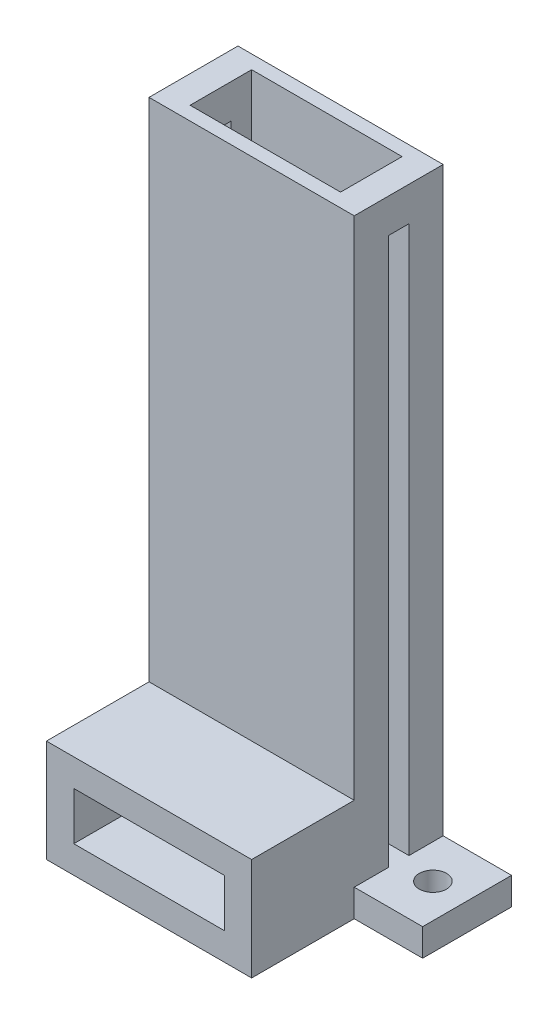
SolidWorks part; units mm, degrees
ref_plane "Front Plane" through (0, 0, 0) normal (0, 0, 1) x (1, 0, 0)
ref_plane "Top Plane" through (0, 0, 0) normal (0, 1, 0) x (1, 0, 0)
ref_plane "Right Plane" through (0, 0, 0) normal (1, 0, 0) x (0, 0, -1)
sketch "Sketch1" plane through (0, 0, 0) normal (0, 1, 0) x (1, 0, 0)
  line L1 (0, 0) -> (30, 0)
  line L2 (0, 0) -> (0, -13)
  line L3 (0, -13) -> (30, -13)
  line L4 (30, 0) -> (30, -13)
  dimension "D1" = 30
  dimension "D2" = 13
extrude "Boss-Extrude1" add sketch "Sketch1" along normal blind 85
sketch "Sketch2" plane through (0, 85, 0) normal (0, 1, 0) x (1, 0, 0)
  line L0 (0, -6.5) -> (30, -6.5) construction
  line L1 (0, 0) -> (0, -13) construction
  line L2 (30, -13) -> (30, 0) construction
  line L4 (4, -11) -> (26, -11)
  line L5 (4, -11) -> (4, -2)
  line L6 (4, -2) -> (26, -2)
  line L7 (26, -11) -> (26, -2)
  line L8 (4, -11) -> (26, -2) construction
  line L9 (4, -2) -> (26, -11) construction
  point P6 (15, -6.5)
  dimension "D1" = 22
  dimension "D2" = 9
extrude "Cut-Extrude2" cut sketch "Sketch2" against normal blind 85
sketch "Sketch5" plane through (0, 0, 0) normal (0, 1, 0) x (1, 0, 0)
  line L1 (0, 0) -> (30, 0)
  line L2 (0, 0) -> (0, -13)
  line L3 (0, -13) -> (30, -13)
  line L4 (30, 0) -> (30, -13)
extrude "Boss-Extrude3" add sketch "Sketch5" against normal blind 4
sketch "Sketch7" plane through (0, 85, 0) normal (0, 1, 0) x (1, 0, 0)
  line L0 (4, -13) -> (4, 0) construction
  line L1 (0, -13) -> (30, -13) construction
  line L2 (30, 0) -> (0, 0) construction
  line L3 (26, -13) -> (26, 0) construction
sketch "Sketch10" plane through (0, 85, 0) normal (0, 1, 0) x (1, 0, 0)
  line L0 (4, -13) -> (0, -13) construction
sketch "Sketch12" plane through (0, 0, 13) normal (0, 0, 1) x (1, 0, 0)
  line L0 (0, -4) -> (0, 0) construction
  line L1 (0, 85) -> (0, -4) construction
  line L2 (0, -4) -> (4, -4) construction
  line L3 (0, -4) -> (30, -4) construction
  line L4 (4, -4) -> (4, 0) construction
  line L5 (4, 0) -> (4, 7) construction
  line L7 (4, 0) -> (26, 0)
  line L8 (4, 0) -> (4, 7)
  line L9 (4, 7) -> (26, 7)
  line L10 (26, 0) -> (26, 7)
  dimension "D1" = 22
extrude "Cut-Extrude4" cut sketch "Sketch12" against normal blind 13 contours L9 L10 L7 L8
sketch "Sketch13" plane through (0, 0, 0) normal (-1, 0, 0) x (0, 0, 1)
  line L0 (0, -4) -> (13, -4) construction
  line L1 (5, -4) -> (8, -4) construction
  line L2 (6.5, -4) -> (6.5, 0) construction
  line L3 (6.5, 0) -> (5, 0) construction
  line L5 (5, 0) -> (8, 0)
  line L6 (5, 0) -> (5, 80)
  line L7 (5, 80) -> (8, 80)
  line L8 (8, 0) -> (8, 80)
  point P7 (6.5, -4)
  dimension "D1" = 3
  dimension "D2" = 80
extrude "Cut-Extrude5" cut sketch "Sketch13" against normal through all
sketch "Sketch14" plane through (0, 0, 13) normal (0, 0, 1) x (1, 0, 0)
  line L0 (30, 85) -> (30, -4) construction
  line L1 (4, 7) -> (26, 7) construction
  line L2 (4, 7) -> (4, 0) construction
  line L3 (4, 0) -> (26, 0) construction
  line L4 (26, 7) -> (26, 0) construction
  line L5 (0, -4) -> (30, -4)
  line L6 (0, -4) -> (0, 11)
  line L7 (0, 11) -> (30, 11)
  line L8 (30, -4) -> (30, 11)
  line L9 (26, 3.5) -> (30, 3.5) construction
  line L10 (15, 7) -> (15, 11) construction
extrude "Boss-Extrude4" add sketch "Sketch14" along normal blind 15
sketch "Sketch15" plane through (0, 0, 28) normal (0, 0, 1) x (1, 0, 0)
  line L0 (0, 3.5) -> (4, 3.5) construction
  line L1 (0, 11) -> (0, -4) construction
  line L2 (15, -4) -> (15, 0) construction
  line L3 (0, -4) -> (30, -4) construction
  line L4 (30, 3.5) -> (26, 3.5) construction
  line L5 (30, -4) -> (30, 11) construction
  line L6 (15, 11) -> (15, 7) construction
  line L7 (30, 11) -> (0, 11) construction
  line L8 (4, 0) -> (26, 0)
  line L9 (26, 0) -> (26, 7)
  line L10 (26, 7) -> (4, 7)
  line L11 (4, 7) -> (4, 0)
extrude "Cut-Extrude6" cut sketch "Sketch15" against normal blind 15
sketch "Sketch16" plane through (0, 0, 0) normal (-1, 0, 0) x (0, 0, 1)
  line L0 (13, 11) -> (0, 11) construction
  line L1 (0, 85) -> (0, -4) construction
  line L3 (0, -4) -> (13, -4)
  line L4 (0, -4) -> (0, 0)
  line L5 (0, 0) -> (13, 0)
  line L6 (13, -4) -> (13, 0)
extrude "Boss-Extrude5" add sketch "Sketch16" along normal blind 10
sketch "Sketch18" plane through (30, 0, 0) normal (1, 0, 0) x (0, 0, -1)
  line L0 (-13, 11) -> (0, 11) construction
  line L1 (-13, 85) -> (-13, 11) construction
  line L2 (-28, 11) -> (-13, 11) construction
  line L3 (0, 85) -> (0, -4) construction
  line L5 (0, -4) -> (-13, -4)
  line L6 (0, -4) -> (0, 0)
  line L7 (0, 0) -> (-13, 0)
  line L8 (-13, -4) -> (-13, 0)
extrude "Boss-Extrude6" add sketch "Sketch18" along normal blind 10
sketch "Sketch19" plane through (0, 0, 0) normal (0, 1, 0) x (1, 0, 0)
  line L0 (-10, -6.5) -> (40, -6.5) construction
  line L1 (-10, -13) -> (-10, 0) construction
  line L2 (40, 0) -> (40, -13) construction
  line L3 (-5, 0) -> (-5, -13) construction
  line L4 (-10, 0) -> (0, 0) construction
  line L5 (-10, -13) -> (0, -13) construction
  line L6 (35, 0) -> (35, -6.5) construction
  line L7 (40, 0) -> (30, 0) construction
  circle A0 centre (-5, -6.5) radius 2
  circle A1 centre (35, -6.5) radius 2
  point P16 (-5, -6.5)
  dimension "D1" = 6.5
extrude "Cut-Extrude7" cut sketch "Sketch19" against normal blind 10
sketch "Sketch20" plane through (0, 0, 0) normal (0, 1, 0) x (1, 0, 0)
  line L0 (-10, 0) -> (0, 0) construction
  point P0 (-5, -6.5)
  point P1 (35, -6.5)
  dimension "D1" = 6.5
  dimension "D2" = 40
